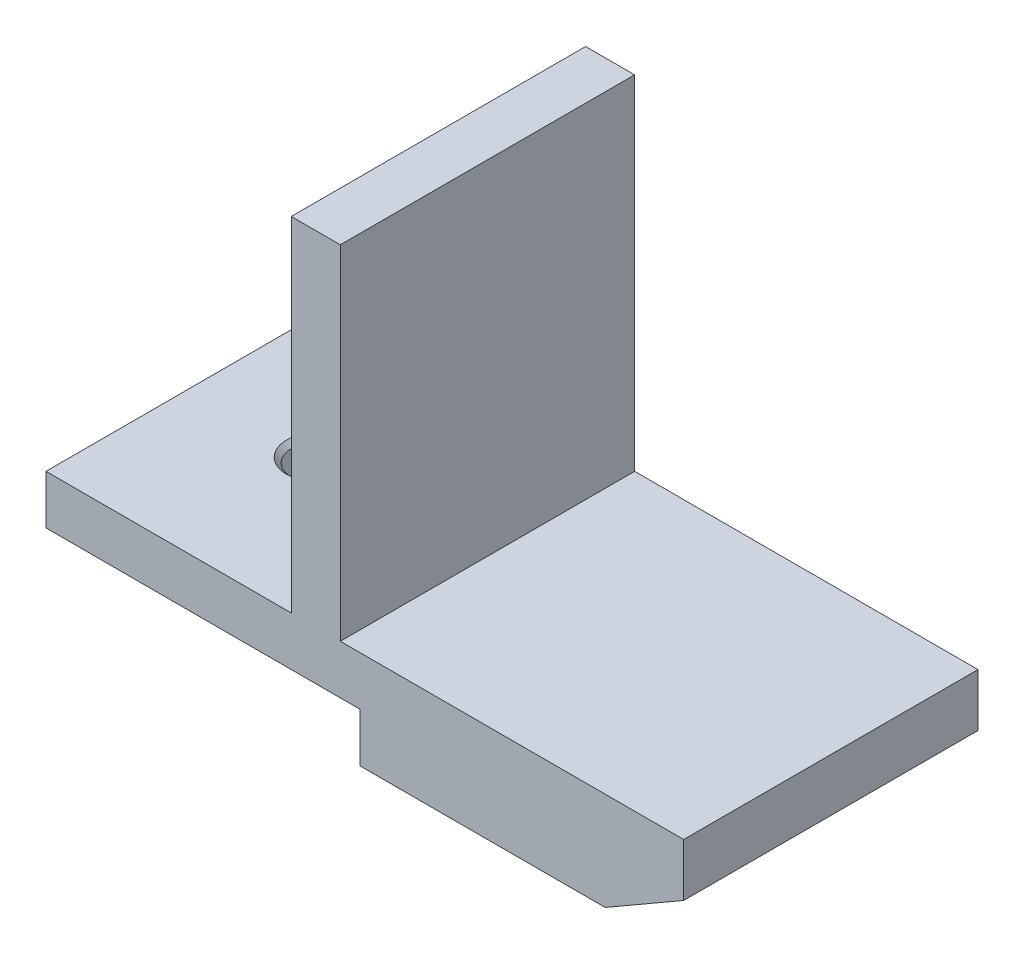
SolidWorks part; units mm, degrees
ref_plane "Front Plane" through (0, 0, 0) normal (0, 0, 1) x (1, 0, 0)
ref_plane "Top Plane" through (0, 0, 0) normal (0, 1, 0) x (1, 0, 0)
ref_plane "Right Plane" through (0, 0, 0) normal (1, 0, 0) x (0, 0, -1)
sketch "Sketch1" plane through (0, 0, 0) normal (0, 0, 1) x (1, 0, 0)
  line L0 (0, 0) -> (44.45, 0)
  line L1 (44.45, 0) -> (44.45, -12.7)
  line L2 (44.45, -12.7) -> (2.54, -12.7)
  line L3 (-38.1, -6.35) -> (-38.1, 0)
  line L4 (-38.1, 0) -> (-6.35, 0)
  line L5 (-6.35, 0) -> (-6.35, 44.45)
  line L6 (-6.35, 44.45) -> (0, 44.45)
  line L7 (0, 44.45) -> (0, 0)
  line L8 (2.54, -12.7) -> (2.54, -6.35)
  line L9 (2.54, -6.35) -> (-38.1, -6.35)
  dimension "D1" = 44.45
  dimension "D2" = 44.45
  dimension "D3" = 12.7
  dimension "D4" = 31.75
  dimension "D5" = 6.35
  dimension "D6" = 6.35
  dimension "D7" = 40.64
extrude "Boss-Extrude1" add sketch "Sketch1" along normal blind 38.1
hole_wizard "1/4 (0.25) Diameter Hole1" positions "Sketch4" profile "Sketch3" hole size "1/4" standard "ANSI Inch" end condition through all
sketch "Sketch4" plane through (0, 0, 0) normal (0, 1, 0) x (1, 0, 0)
  line L0 (-6.35, 0) -> (-38.1, 0) construction
  point P0 (-22.225, -19.05)
  point P5 (-22.225, 0)
sketch "Sketch3" plane through (-22.225, 0, 19.05) normal (1, 0, 0) x (0, 0, 1)
  line L0 (0, 0) -> (0, 12.7)
  line L1 (0, 12.7) -> (3.175, 12.7)
  line L2 (3.175, 12.7) -> (3.175, 0.635)
  line L3 (3.175, 0.635) -> (3.81, 0)
  line L5 (3.81, 0) -> (0, 0)
  line L6 (-3.175, 0.635) -> (-3.81, 0) construction
  line L11 (0, -6.35) -> (0, 107.95) construction
  dimension "Thru Hole Dia." = 6.35
  dimension "Thru Hole Depth" = 12.7
  dimension "Near C'Sink Dia." = 7.62
  dimension "Near C'Sink Angle" = 90
chamfer "Chamfer1" distance 10.16 angle 30 1 edges at (44.45, -12.7, 19.05) first distance on face at (23.495, -12.7, 19.05)
